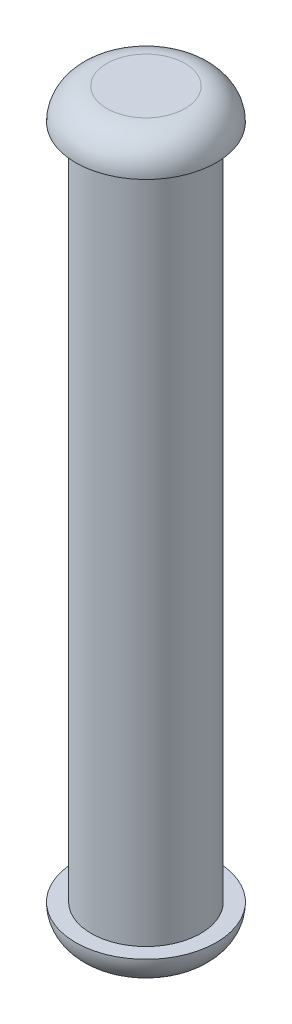
SolidWorks part; units mm, degrees
material "AISI 304"
ref_plane "Front Plane" through (0, 0, 0) normal (0, 0, 1) x (1, 0, 0)
ref_plane "Top Plane" through (0, 0, 0) normal (0, 1, 0) x (1, 0, 0)
ref_plane "Right Plane" through (0, 0, 0) normal (1, 0, 0) x (0, 0, -1)
sketch "Sketch1" plane through (0, 0, 0) normal (0, 1, 0) x (1, 0, 0)
  circle A0 centre (0, 0) radius 1.75
  dimension "D1" = 3.5
extrude "Boss-Extrude1" add sketch "Sketch1" along normal mid plane 21.6
sketch "Sketch2" plane through (0, 10.8, 0) normal (0, 1, 0) x (1, 0, 0)
  circle A0 centre (0, 0) radius 2.25
  dimension "D1" = 4.5
extrude "Boss-Extrude2" add sketch "Sketch2" along normal blind 1
mirror "Mirror1" about plane through (0, 0, 0) normal (0, 1, 0) of "Boss-Extrude2"
fillet "Fillet1" radius 1 2 edges at (0, -11.8, 2.25) (0, 11.8, 2.25)
